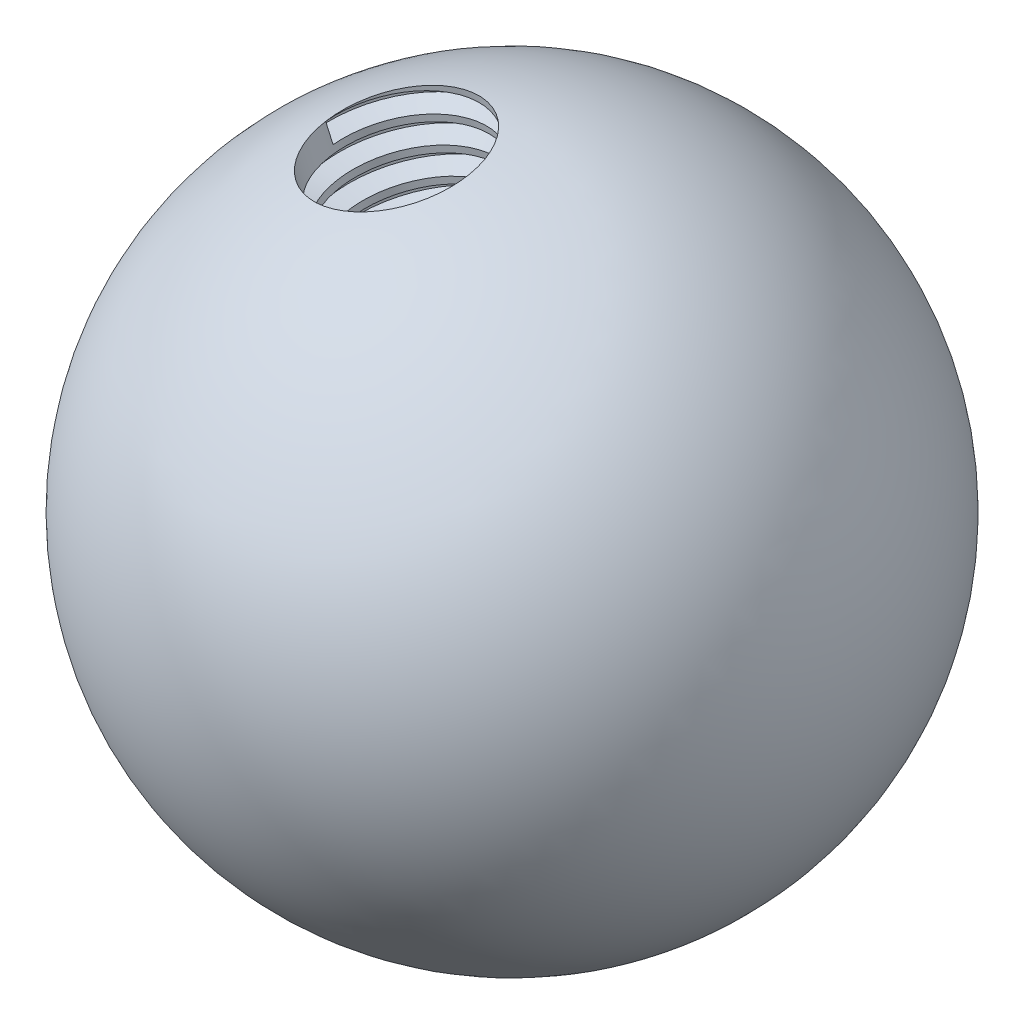
SolidWorks part; units mm, degrees
material "AISI 316L"
ref_plane "Piano frontale" through (0, 0, 0) normal (0, 0, 1) x (1, 0, 0)
ref_plane "Piano superiore" through (0, 0, 0) normal (0, 1, 0) x (1, 0, 0)
ref_plane "Piano destro" through (0, 0, 0) normal (1, 0, 0) x (0, 0, -1)
sketch "Schizzo1" plane through (0, 0, 0) normal (0, 0, 1) x (1, 0, 0)
  line L0 (0.6636, 14.9853) -> (-0.6636, -14.9853)
  arc A0 (0.6636, 14.9853) -> (-0.6636, -14.9853) centre (0, 0) ccw
  dimension "D1" = 30
revolve "Rivoluzione1" add sketch "Schizzo1" angle 360 about L0
hole_wizard "Preforo da maschiare M8x1.25-1" positions "Schizzo3D1" profile "Schizzo2" hole size "M8x1.25" standard "Ansi Metric"
sketch3d "Schizzo3D1"
  point P0 (0, 0, 0)
  point P3 (0, 0, 0)
  point P5 (-2.9015, 14.5029, 2.4995)
sketch "Schizzo2" plane through (-2.9015, 14.5029, 2.4995) normal (0.707, 0.0196, 0.707) x (-0.6803, -0.2546, 0.6873)
  line L0 (0, 0) -> (0, 16.5)
  line L1 (0, 16.5) -> (3.4, 14.4571)
  line L2 (3.4, 14.4571) -> (3.4, 0)
  line L5 (3.4, 0) -> (0, 0)
  line L10 (0, 16.5) -> (-3.4, 14.4571) construction
  line L11 (0, -6.35) -> (0, 107.95) construction
  dimension "Hole Dia." = 6.8
  dimension "Hole Depth" = 16.5
  dimension "Drill Angle" = 118
thread "Filettatura1" pitch 1.25 method cut profile "Profilo filettatura1" start angle 0, offset 0, length 15, pitch 1.25, diameter 6.8
ref_plane "Piano1" through (-6.1618, 13.4773, 2.3228) normal (0, -0.1698, 0.9855) x (-0.9811, -0.1906, -0.0329)
sketch "Profilo filettatura1" plane through (-6.1618, 13.4773, 2.3228) normal (0, -0.1698, 0.9855) x (-0.9811, -0.1906, -0.0329)
  line L0 (0, 0) -> (0, 1.25) construction
  line L1 (0, 0) -> (0.6766, 0.3906)
  line L2 (0.6766, 0.3906) -> (0.6766, 0.5469)
  line L3 (0.6766, 0.5469) -> (0, 0.9375)
  line L4 (0.6766, 0.4687) -> (0, 0.4687) construction
  line L11 (0, 0) -> (0, 0.9375)
  point P2 (0, 0)
  dimension "Pitch" = 1.25
  dimension "Profile_Angle" = 60
  dimension "Profile_Land" = 0.1562
  dimension "Profile_Height" = 0.6766
